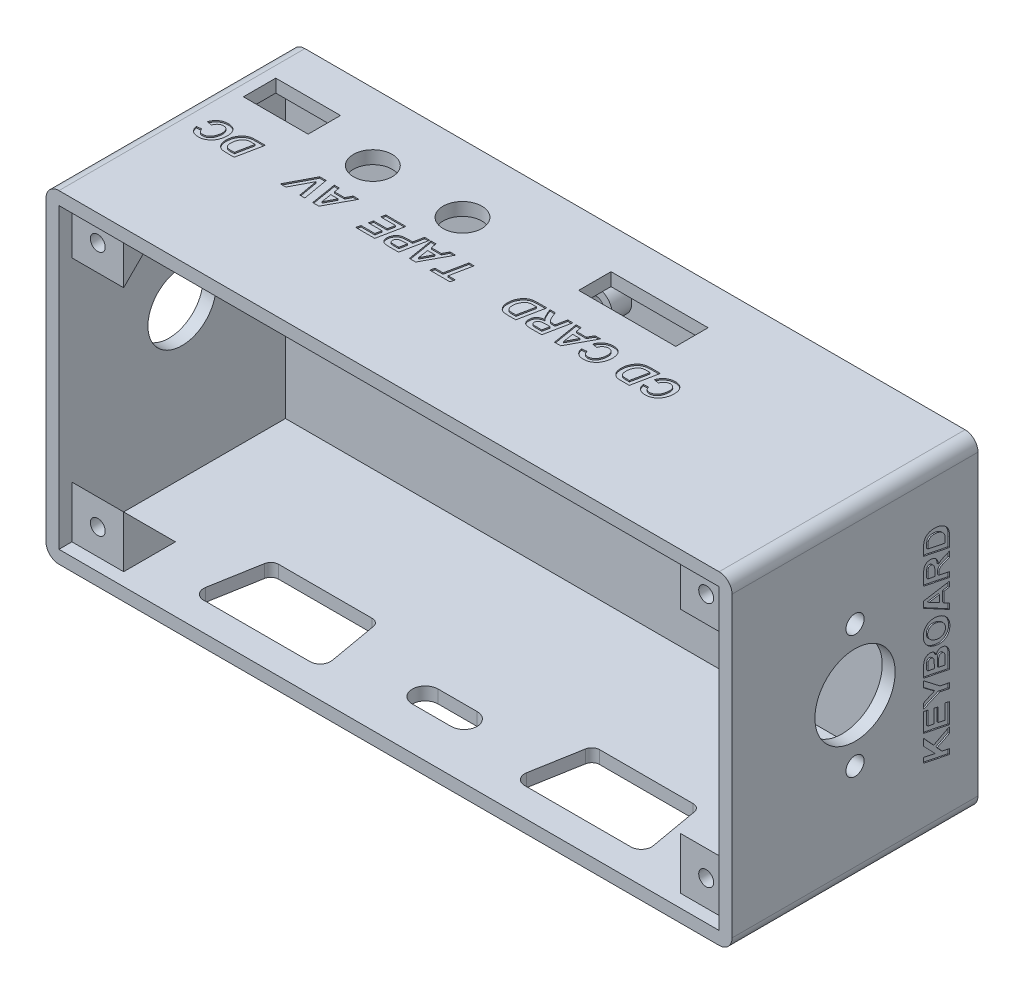
SolidWorks part; units mm, degrees
material "ABS"
ref_plane "Спереди" through (0, 0, 0) normal (0, 0, 1) x (1, 0, 0)
ref_plane "Сверху" through (0, 0, 0) normal (0, 1, 0) x (1, 0, 0)
ref_plane "Справа" through (0, 0, 0) normal (1, 0, 0) x (0, 0, -1)
sketch "Эскиз1" plane through (0, 0, 0) normal (0, 0, 1) x (1, 0, 0)
  line L1 (-53, -25) -> (53, -25)
  line L2 (-53, -25) -> (-53, 25)
  line L3 (-53, 25) -> (53, 25)
  line L4 (53, -25) -> (53, 25)
  line L5 (-53, -25) -> (53, 25) construction
  line L6 (-53, 25) -> (53, -25) construction
  point P0 (0, 0)
  dimension "D1" = 106
  dimension "D2" = 50
extrude "CaseBody" add sketch "Эскиз1" along normal blind 3
sketch "Эскиз2" plane through (0, 0, 3) normal (0, 0, 1) x (1, 0, 0)
  line L0 (53, 25) -> (-53, 25) construction
  line L1 (-51, -23) -> (51, -23)
  line L2 (-51, -23) -> (-51, 23)
  line L3 (-51, 23) -> (51, 23)
  line L4 (51, -23) -> (51, 23)
  line L5 (-51, -23) -> (51, 23) construction
  line L6 (-51, 23) -> (51, -23) construction
  line L7 (53, -25) -> (53, 25) construction
  line L9 (-53, -25) -> (53, -25)
  line L10 (-53, -25) -> (-53, 25)
  line L11 (-53, 25) -> (53, 25)
  line L12 (53, -25) -> (53, 25)
  line L13 (-53, -25) -> (53, 25) construction
  line L14 (-53, 25) -> (53, -25) construction
  point P0 (0, 0)
  point P10 (0, 0)
  dimension "D1" = 2
  dimension "D2" = 2
extrude "CaseBody2" add sketch "Эскиз2" along normal blind 35
sketch "Эскиз3" plane through (0, 0, 3) normal (0, 0, 1) x (1, 0, 0)
  line L0 (51, 23) -> (-51, 23) construction
  line L1 (-46.625, 1.53) -> (46.625, 1.53) construction
  line L2 (-46.625, 1.53) -> (-46.625, 19.18) construction
  line L3 (-46.625, 19.18) -> (46.625, 19.18) construction
  line L4 (46.625, 1.53) -> (46.625, 19.18) construction
  line L5 (-46.625, 1.53) -> (46.625, 19.18) construction
  line L6 (-46.625, 19.18) -> (46.625, 1.53) construction
  circle A0 centre (-46.625, 1.53) radius 2.5
  circle A1 centre (46.625, 1.53) radius 2.5
  circle A2 centre (0.005, 19.18) radius 2.5
  point P0 (0, 0)
  point P13 (0, 10.355)
  dimension "D4" = 5
  dimension "D1" = 93.25
  dimension "D2" = 17.65
  dimension "D3" = 46.63
  dimension "D5" = 3.82
extrude "SizifXXSFix" add sketch "Эскиз3" along normal blind 3
sketch "Эскиз4" plane through (0, 0, 6) normal (0, 0, 1) x (1, 0, 0)
  circle A0 centre (-46.625, 1.53) radius 1.2
  circle A1 centre (0.005, 19.18) radius 1.2
  circle A2 centre (46.625, 1.53) radius 1.2
  dimension "D1" = 2.4
extrude "Holes2_5" cut sketch "Эскиз4" against normal blind 5.6
sketch "Эскиз5" plane through (0, 25, 0) normal (0, 1, 0) x (1, 0, 0)
  line L1 (-49.3, -6.2) -> (-39.3, -6.2)
  line L2 (-49.3, -6.2) -> (-49.3, -11.2)
  line L3 (-49.3, -11.2) -> (-39.3, -11.2)
  line L4 (-39.3, -6.2) -> (-39.3, -11.2)
  line L5 (-49.3, -6.2) -> (-39.3, -11.2) construction
  line L6 (-49.3, -11.2) -> (-39.3, -6.2) construction
  line L7 (2.5, -6.2) -> (17.5, -6.2)
  line L8 (2.5, -6.2) -> (2.5, -11.2)
  line L9 (2.5, -11.2) -> (17.5, -11.2)
  line L10 (17.5, -6.2) -> (17.5, -11.2)
  line L11 (2.5, -6.2) -> (17.5, -11.2) construction
  line L12 (2.5, -11.2) -> (17.5, -6.2) construction
  line L13 (53, 0) -> (-53, 0) construction
  line L14 (-53, -38) -> (-53, 0) construction
  circle A0 centre (-30.1, -10.4) radius 3
  circle A1 centre (-16.25, -10.4) radius 3
  point P0 (-44.3, -8.7)
  point P9 (10, -8.7)
  dimension "D5" = 6
  dimension "D2" = 10
  dimension "D3" = 6.2
  dimension "D4" = 5
  dimension "D6" = 13.85
  dimension "D7" = 14.2
  dimension "D8" = 26.25
  dimension "D9" = 10.4
  dimension "D10" = 5
  dimension "D11" = 15
  dimension "D12" = 22.9
extrude "SizifXXS_Holes" cut sketch "Эскиз5" against normal up to next
sketch "Эскиз7" plane through (53, 0, 0) normal (1, 0, 0) x (0, 0, -1)
  line L0 (-20, 0) -> (-6.0564, 0) construction
  line L2 (0, -25) -> (0, 25) construction
  circle A0 centre (-19, 0) radius 6.2
  circle A1 centre (-19, -9.5) radius 1.4
  circle A2 centre (-19, 9.5) radius 1.4
  dimension "D1" = 12.4
  dimension "D4" = 2.8
  dimension "D2" = 19
  dimension "D3" = 19
extrude "PS2Hole" cut sketch "Эскиз7" against normal up to next
sketch "Эскиз8" plane through (51, 0, 0) normal (-1, 0, 0) x (0, 0, 1)
  line L0 (36, 23) -> (36, 15)
  line L1 (38, 23) -> (3, 23) construction
  line L2 (36, 15) -> (28, 23)
  line L3 (28, 23) -> (36, 23)
  line L4 (38, -23) -> (38, 23) construction
  dimension "D1" = 8
  dimension "D2" = 8
  dimension "D3" = 2
extrude "CaseTopFix" add sketch "Эскиз8" along normal blind 8
sketch "Эскиз9" plane through (0, 0, 36) normal (0, 0, 1) x (1, 0, 0)
  line L0 (43, 15) -> (43, 23) construction
  line L1 (43, 23) -> (51, 23) construction
  line L2 (43, 23) -> (43, 15) construction
  line L3 (43, 15) -> (51, 15) construction
  line L4 (51, 23) -> (51, 15) construction
  line L5 (43, 23) -> (51, 15) construction
  line L6 (43, 15) -> (51, 23) construction
  line L7 (43, 23) -> (51, 23) construction
  circle A0 centre (47, 19) radius 1.15
  point P0 (47, 19)
  dimension "D1" = 2.3
extrude "CaseTopHoles" cut sketch "Эскиз9" against normal up to next
mirror "CaseTopHoles1" about plane through (0, 0, 0) normal (0, 1, 0) of "CaseTopHoles", "CaseTopFix"
mirror "CaseTopHoles2" about plane through (0, 0, 0) normal (1, 0, 0) of "CaseTopHoles", "CaseTopHoles1", "CaseTopFix"
fillet "Fillet" radius 2 4 edges at (-53, 25, 19) (53, 25, 19) (53, -25, 19) (-53, -25, 19)
sketch "Эскиз10" plane through (0, 25, 0) normal (0, 1, 0) x (1, 0, 0)
  line L0 (51, 0) -> (-51, 0) construction
  line L1 (-53, -38) -> (-53, 0) construction
  text T0 "<r180>VA</r>" font "Times New Roman" height 4
  text T1 "<r180>EPAT</r>" font "Times New Roman" height 4
  text T2 "<r180>CD</r>" font "Times New Roman" height 4
  text T3 "<r180>DRAC DC</r>" font "Times New Roman" height 4
  dimension "D1" = 16
  dimension "D2" = 22.5962
  dimension "D3" = 11.2585
  dimension "D4" = 14.4528
  dimension "D5" = 21.8
extrude "InterfaceInfo" cut sketch "Эскиз10" against normal blind 0.2
sketch "Эскиз11" plane through (53, 0, 0) normal (1, 0, 0) x (0, 0, -1)
  line L0 (-4.4, -15.5) -> (-4.4, 15.5) construction
  line L1 (0, -23) -> (0, 23) construction
  text T0 "KEYBOARD" font "Arial" height 4
  point P0 (-4.4, 0)
  dimension "D1" = 4.4
  dimension "D2" = 31
extrude "PS2Info" cut sketch "Эскиз11" against normal blind 0.2
sketch "Эскиз12" plane through (0, 23, 0) normal (0, -1, 0) x (1, 0, 0)
  line L1 (-53, 0) -> (-53, 38) construction
  line L2 (-51, 0) -> (51, 0) construction
  text T0 "© Peter Ukhov 2023" font "Arial" height 6
  dimension "D1" = 28
  dimension "D2" = 14
sketch "Эскиз13" plane through (-53, 0, 0) normal (-1, 0, 0) x (0, 0, 1)
  line L1 (0, 23) -> (0, -23) construction
  circle A0 centre (19, 0) radius 5.25
  dimension "D1" = 10.5
  dimension "D2" = 19
extrude "ButtonHole" cut sketch "Эскиз13" against normal up to next
sketch "Эскиз14" plane through (-53, 0, 0) normal (-1, 0, 0) x (0, 0, 1)
  line L0 (6.2274, 10.1387) -> (6.2274, -12.1287) construction
  text T0 "POWER" font "Arial" height 4
extrude "ButtonInfo" cut sketch "Эскиз14" against normal blind 0.2
extrude "CopyLeft" cut sketch "Эскиз12" against normal blind 0.2
sketch "Эскиз15" plane through (0, -25, 0) normal (0, -1, 0) x (1, 0, 0)
  line L0 (-3, 29.4) -> (3, 29.4) construction
  line L1 (-3, 31.4) -> (3, 31.4)
  line L2 (-3, 27.4) -> (3, 27.4)
  line L3 (-51, 38) -> (51, 38) construction
  arc A0 (-3, 31.4) -> (-3, 27.4) centre (-3, 29.4) ccw
  arc A1 (3, 27.4) -> (3, 31.4) centre (3, 29.4) ccw
  point P2 (0, 29.4)
  dimension "D1" = 4
  dimension "D2" = 6
  dimension "D3" = 8.6
extrude "USBArduinoNano" cut sketch "Эскиз15" against normal up to next
sketch "Эскиз16" plane through (0, -25, 0) normal (0, -1, 0) x (1, 0, 0)
  line L0 (-34.5757, 31.755) -> (-33.2126, 24.0245)
  line L1 (-32.0308, 23.0329) -> (-17.5692, 23.0329)
  line L2 (-16.3874, 24.0245) -> (-15.0243, 31.755)
  line L3 (-16.6, 33.6329) -> (-33, 33.6329)
  line L4 (-33, 33.6329) -> (-17.5692, 23.0329) construction
  line L5 (-32.0308, 23.0329) -> (-16.6, 33.6329) construction
  line L6 (-51, 38) -> (51, 38) construction
  arc A0 (-15.0243, 31.755) -> (-16.6, 33.6329) centre (-16.6, 32.0329) ccw
  arc A1 (-33, 33.6329) -> (-34.5757, 31.755) centre (-33, 32.0329) ccw
  arc A2 (-17.5692, 23.0329) -> (-16.3874, 24.0245) centre (-17.5692, 24.2329) ccw
  arc A3 (-33.2126, 24.0245) -> (-32.0308, 23.0329) centre (-32.0308, 24.2329) ccw
  point P0 (-24.8, 28)
  dimension "D1" = 1.6
  dimension "D2" = 1.2
  dimension "D3" = 24.8
  dimension "D4" = 10
  dimension "D5" = 16.4
  dimension "D7" = 10.6
  dimension "D8" = 80
  dimension "D9" = 80
extrude "NESCut1" cut sketch "Эскиз16" against normal up to next
mirror "NESCut2" about plane through (0, 0, 0) normal (1, 0, 0) of "NESCut1"
sketch "Эскиз17" plane through (0, -25, 0) normal (0, -1, 0) x (1, 0, 0)
  line L0 (-51, 0) -> (51, 0) construction
  line L1 (-51, 38) -> (-51, 0) construction
  text T0 "<b>JOYSTICK1</b>"
  text T1 "<b>JOYSTICK2</b>"
  point P1 (-40.3656, 14.3521)
  point P7 (0, 0)
  point P8 (11.4324, 14)
  point P9 (0, 0)
  point P10 (0, 0)
  point P11 (10.6277, 14)
  dimension "D1" = 14
  dimension "D2" = 10.4
  dimension "D3" = 50
extrude "Вырез-Вытянуть1" cut sketch "Эскиз17" against normal blind 0.2
equation "\"D1@Эскиз1\"=100+2*2+2"
equation "\"D5@Эскиз3\"=3.42+0.4"
equation "\"D2@Эскиз15\"=10-2-2"
equation "\"12ю5\"=12"
